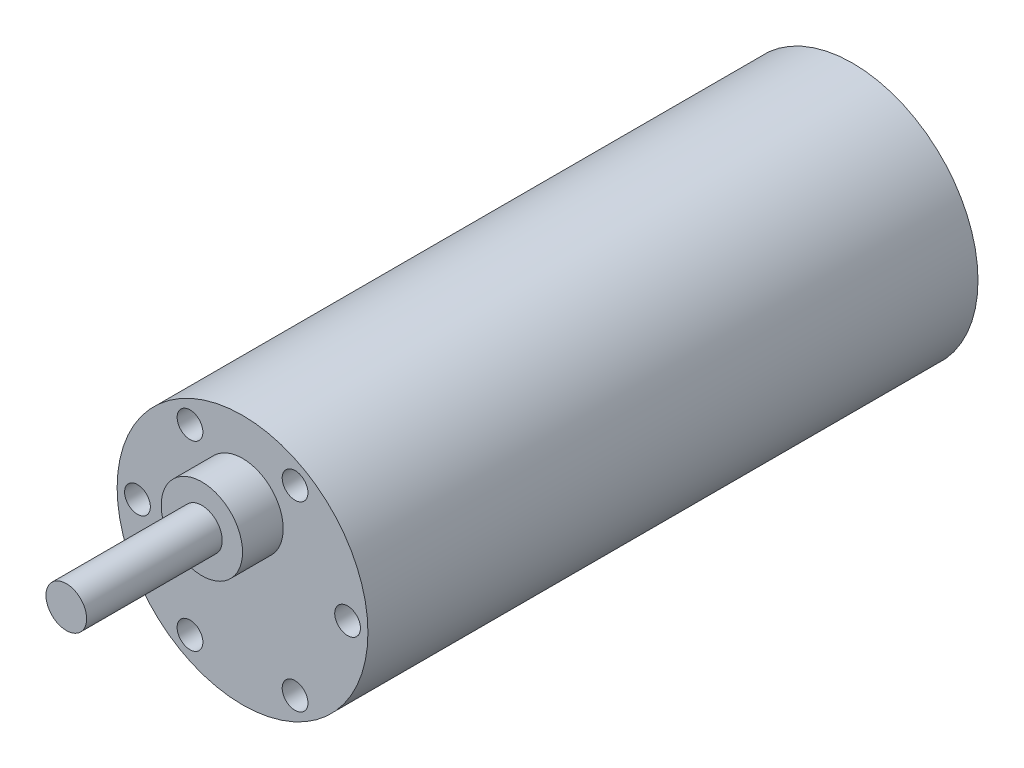
SolidWorks part; units mm, degrees
ref_plane "Front Plane" through (0, 0, 0) normal (1, 0, 0) x (0, 1, 0)
ref_plane "Top Plane" through (0, 0, 0) normal (0, 0, 1) x (0, 1, 0)
ref_plane "Right Plane" through (0, 0, 0) normal (0, 1, 0) x (-1, 0, 0)
sketch "Sketch1" plane through (0, 0, 0) normal (0, 0, 1) x (0, 1, 0)
  circle A0 centre (0, 0) radius 18.5
  dimension "D1" = 37
extrude "Boss-Extrude1" add sketch "Sketch1" along normal blind 90
sketch "Sketch2" plane through (0, 0, 90) normal (0, 0, 1) x (-1, 0, 0)
  circle A7 centre (0, -7) radius 6
  circle A9 centre (0, 0) radius 18.5 construction
  circle A21 centre (0, 0) radius 15.5 construction
  circle A22 centre (-15.5, 0) radius 1.9
  circle A23 centre (-7.75, 13.4234) radius 1.9
  circle A24 centre (7.75, 13.4234) radius 1.9
  circle A25 centre (15.5, 0) radius 1.9
  circle A26 centre (7.75, -13.4234) radius 1.9
  circle A27 centre (-7.75, -13.4234) radius 1.9
  dimension "D2" = 37
  dimension "D14" = 31
  dimension "D15" = 3.8
  dimension "D6" = 12
  dimension "D13" = 7
  dimension "D16" = 6
extrude "Cut-Extrude1" cut sketch "Sketch2" against normal blind 3 contours A22 | A23 | A24 | A25 | A26 | A27 region at (15.5, 0, 90) region at (7.75, -13.4234, 90) region at (-7.75, -13.4234, 90) region at (-15.5, 0, 90) region at (-7.75, 13.4234, 90) region at (7.75, 13.4234, 90)
extrude "Boss-Extrude2" add sketch "Sketch2<3>" along normal blind 6 contours A7 region at (0, 7, 90)
sketch "Sketch2<3>" plane through (0, 0, 90) normal (0, 0, 1) x (-1, 0, 0) same geometry as "Sketch2"
sketch "Sketch3" plane through (0, 0, 96) normal (0, 0, 1) x (1, 0, 0)
  circle A0 centre (0, 7) radius 3
  dimension "D1" = 6
extrude "Boss-Extrude3" add sketch "Sketch3" along normal blind 20
